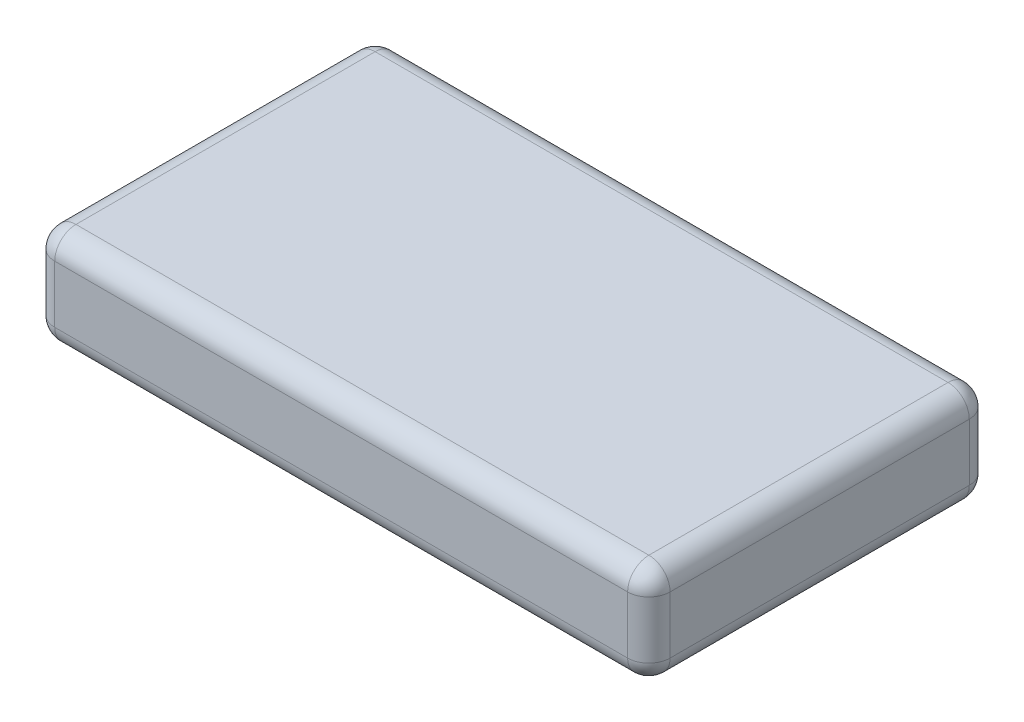
SolidWorks part; units mm, degrees
ref_plane "Front Plane" through (0, 0, 0) normal (0, 0, 1) x (1, 0, 0)
ref_plane "Top Plane" through (0, 0, 0) normal (0, 1, 0) x (1, 0, 0)
ref_plane "Right Plane" through (0, 0, 0) normal (1, 0, 0) x (0, 0, -1)
sketch "Sketch1" plane through (0, 0, 0) normal (0, 1, 0) x (1, 0, 0)
  line L1 (-29, 16.1) -> (29, 16.1)
  line L2 (-29, 16.1) -> (-29, -16.1)
  line L3 (-29, -16.1) -> (29, -16.1)
  line L4 (29, 16.1) -> (29, -16.1)
  line L5 (-29, 16.1) -> (29, -16.1) construction
  line L6 (-29, -16.1) -> (29, 16.1) construction
  point P0 (0, 0)
  dimension "D1" = 32.2
  dimension "D2" = 58
extrude "Boss-Extrude1" add sketch "Sketch1" along normal blind 9.4
fillet "Fillet1" radius 2 12 edges at (29, 4.7, -16.1) (-29, 4.7, -16.1) (0, 0, -16.1) (-29, 0, 0) (29, 0, 0) (-29, 4.7, 16.1) (29, 4.7, 16.1) (0, 0, 16.1) (0, 9.4, 16.1) (-29, 9.4, 0) (0, 9.4, -16.1) (29, 9.4, 0)
